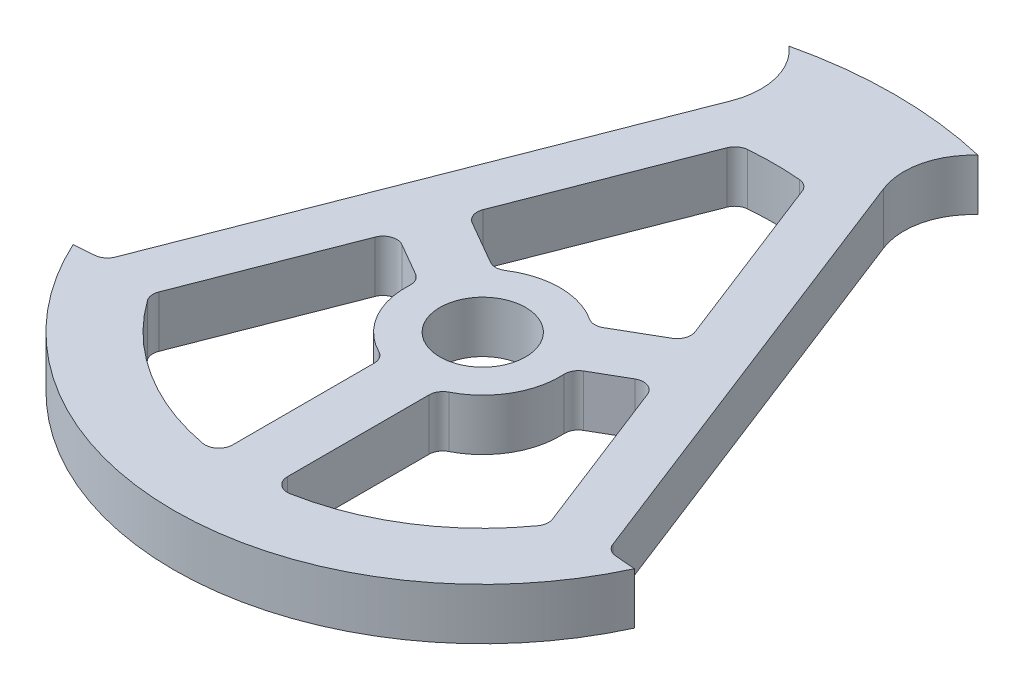
SolidWorks part; units mm, degrees
material "AISI Type A2 Tool Steel"
ref_plane "Front Plane" through (0, 0, 0) normal (0, 0, 1) x (1, 0, 0)
ref_plane "Top Plane" through (0, 0, 0) normal (0, 1, 0) x (1, 0, 0)
ref_plane "Right Plane" through (0, 0, 0) normal (1, 0, 0) x (0, 0, -1)
other "Center of Mass"
other "Bounding Box"
ref_plane "Default Plane" through (-8.9266, -12.7485, 0) normal (-0.1736, 0.9848, 0) x (0.9848, 0.1736, 0)
sketch "Sketch1" plane through (0, 0, 0) normal (0, 1, 0) x (1, 0, 0)
  circle A0 centre (0, 0) radius 7.9375
  circle A1 centre (0, 0) radius 34.925
  circle A2 centre (0, 0) radius 76.2 construction
  dimension "D1" = 15.875
  dimension "D2" = 152.4
  dimension "D3" = 69.85
extrude "Boss-Extrude1" add sketch "Sketch1" along normal mid plane 9.525
sketch "Sketch2" plane through (0, 4.7625, 0) normal (0, 1, 0) x (1, 0, 0)
  line L0 (-48.9569, -29.4846) -> (-14.0847, 60.0901)
  line L1 (48.9569, -29.4846) -> (14.0847, 60.0901)
  line L2 (-17.4625, 74.1721) -> (17.4625, 74.1721) construction
  line L3 (0, 0) -> (0, 76.2) construction
  line L4 (0, 0) -> (17.4625, 74.1721) construction
  line L5 (17.4625, 74.1721) -> (-75.6715, -8.959) construction
  line L6 (-48.9569, -29.4846) -> (0, -29.4846) construction
  line L7 (0, -29.4846) -> (48.9569, -29.4846) construction
  circle A0 centre (0, 0) radius 7.9375 construction
  circle A1 centre (0, 0) radius 76.2 construction
  arc A2 (-17.4625, 74.1721) -> (17.4625, 74.1721) centre (0, 0) cw
  arc A3 (14.0847, 60.0901) -> (17.4625, 74.1721) centre (25.9195, 64.6975) cw
  circle A5 centre (0, 0) radius 7.9375
  arc A6 (-14.0847, 60.0901) -> (-17.4625, 74.1721) centre (-25.9195, 64.6975) ccw
  circle A7 centre (0, 0) radius 34.925 construction
  arc A8 (-48.9569, -29.4846) -> (48.9569, -29.4846) centre (0, 0) ccw
  circle A9 centre (0, 0) radius 76.2 construction
  dimension "D1" = 35
  dimension "D3" = 12.7
  dimension "D2" = 19.05
  dimension "D5" = 152.4
  dimension "D4" = 34.925
extrude "Boss-Extrude2" add sketch "Sketch2" against normal up to surface (9.525 mm away) up to face at (0, -4.7625, 34.925)
sketch "Sketch5" plane through (0, 4.7625, 0) normal (0, 1, 0) x (1, 0, 0)
  line L0 (0, 0) -> (30.6003, 17.6671) construction
  line L1 (-20.3903, 17.6382) -> (-6.3919, 53.5952)
  line L2 (6.3919, 53.5952) -> (20.3903, 17.6382)
  line L3 (48.9569, -29.4846) -> (14.0847, 60.0901) construction
  line L4 (-14.0847, 60.0901) -> (-48.9569, -29.4846) construction
  line L5 (-6.3919, 53.5952) -> (-15.268, 57.0507) construction
  line L6 (13.3911, 35.6167) -> (22.2672, 39.0722) construction
  line L7 (0, 0) -> (-30.6003, 17.6671) construction
  line L8 (-14.0847, 60.0901) -> (-48.9569, -29.4846) construction
  line L9 (48.9569, -29.4846) -> (14.0847, 60.0901) construction
  line L10 (0, 0) -> (0, -57.15) construction
  line L11 (14.1048, 2.2775) -> (24.1193, 8.0594)
  line L12 (-5.08, -13.3539) -> (-5.08, -44.1588)
  line L13 (-5.08, -13.3539) -> (0, -13.3539) construction
  line L15 (0, -13.3539) -> (5.08, -13.3539) construction
  line L16 (9.0248, 11.0764) -> (20.3903, 17.6382)
  line L17 (-24.1193, 8.0594) -> (-36.9032, -24.7781)
  line L18 (24.1193, 8.0594) -> (36.9032, -24.7781)
  line L20 (14.1048, 2.2775) -> (11.5648, 6.6769) construction
  line L21 (-14.1048, 2.2775) -> (-24.1193, 8.0594)
  line L22 (-9.0248, 11.0764) -> (-20.3903, 17.6382)
  line L23 (-2.54, 4.3994) -> (28.0603, 22.0665) construction
  line L24 (5.08, -13.3539) -> (5.08, -44.1588)
  line L25 (11.5648, 6.6769) -> (9.0248, 11.0764) construction
  line L26 (-5.08, 0) -> (-5.08, -57.15) construction
  line L27 (-14.1048, 2.2775) -> (-11.5648, 6.6769) construction
  line L28 (-11.5648, 6.6769) -> (-9.0248, 11.0764) construction
  arc A1 (-36.9032, -24.7781) -> (-5.08, -44.1588) centre (0, 0) ccw
  arc A3 (6.3919, 53.5952) -> (-6.3919, 53.5952) centre (0, 0) ccw
  arc A4 (5.08, -44.1588) -> (36.9032, -24.7781) centre (0, 0) ccw
  circle A5 centre (0, 0) radius 76.2 construction
  arc A6 (-14.1048, 2.2775) -> (-5.08, -13.3539) centre (0, 0) ccw
  arc A7 (9.0248, 11.0764) -> (-9.0248, 11.0764) centre (0, 0) ccw
  arc A8 (-48.9569, -29.4846) -> (48.9569, -29.4846) centre (0, 0) ccw construction
  arc A9 (5.08, -13.3539) -> (14.1048, 2.2775) centre (0, 0) ccw
  dimension "D1" = 9.525
  dimension "D2" = 120
  dimension "D3" = 22.225
  dimension "D7" = 12.7
  dimension "D8" = 28.575
  dimension "D4" = 120
  dimension "D5" = 10.16
extrude "Cut-Extrude2" cut sketch "Sketch5" against normal through all
sketch "Sketch6" plane through (0, 4.7625, 0) normal (0, 1, 0) x (1, 0, 0)
  line L0 (0, 0) -> (-51.9257, -23.8714) construction
  line L1 (-51.9257, -23.8714) -> (75.0018, -13.46) construction
  line L2 (-51.9257, -23.8714) -> (-46.6016, -23.4347)
  line L3 (-14.0847, 60.0901) -> (-48.9569, -29.4846) construction
  line L4 (-48.9569, -29.4846) -> (-51.9257, -23.8714) construction
  line L5 (-48.9569, -29.4846) -> (-46.6016, -23.4347)
  circle A0 centre (0, 0) radius 76.2 construction
  arc A1 (-48.9569, -29.4846) -> (-51.9257, -23.8714) centre (0, 0) cw
  dimension "D1" = 6.35
  dimension "D2" = 20
extrude "Boss-Extrude3" add sketch "Sketch6" against normal up to surface (9.525 mm away) up to face at (0, -4.7625, -28.0351)
mirror "Mirror1" about plane through (0, 0, 0) normal (1, 0, 0) of "Boss-Extrude3"
fillet "Fillet2" radius 2.54 16 edges at (-6.3919, 0, -53.5952) (6.3919, 0, -53.5952) (36.9032, 0, 24.7781) (24.1193, 0, -8.0594) (14.1048, 0, -2.2775) (5.08, 0, 13.3539) (5.08, 0, 44.1588) (-5.08, 0, 44.1588) (-36.9032, 0, 24.7781) (-24.1193, 0, -8.0594) (-5.08, 0, 13.3539) (-14.1048, 0, -2.2775) (-9.0248, 0, -11.0764) (9.0248, 0, -11.0764) (20.3903, 0, -17.6382) (-20.3903, 0, -17.6382)
fillet "Fillet3" radius 2.54 2 edges at (46.6016, 0, 23.4347) (-46.6016, 0, 23.4347)
